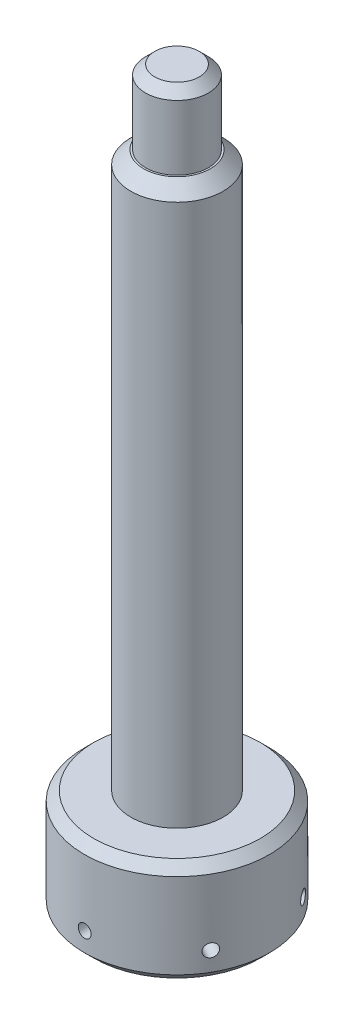
SolidWorks part; units mm, degrees
material "Plain Carbon Steel"
ref_plane "Front Plane" through (0, 0, 0) normal (0, 0, 1) x (1, 0, 0)
ref_plane "Top Plane" through (0, 0, 0) normal (0, 1, 0) x (1, 0, 0)
ref_plane "Right Plane" through (0, 0, 0) normal (1, 0, 0) x (0, 0, -1)
other "Configuration Table"
sketch "Sketch1" plane through (0, 0, 0) normal (0, 1, 0) x (1, 0, 0)
  circle A0 centre (0, 0) radius 6.35
  dimension "D1" = 12.7
extrude "Extrude1" add sketch "Sketch1" along normal blind 4.572
sketch "Sketch4" plane through (0, 0, 0) normal (0, -1, 0) x (1, 0, 0)
  circle A1 centre (0, 0) radius 6.35
  circle A2 centre (0, 0) radius 6.35
  dimension "D1" = 0
extrude "Extrude4" add sketch "Sketch4" along normal blind 1.27
sketch "Sketch5" plane through (0, 4.572, 0) normal (0, 1, 0) x (1, 0, 0)
  circle A1 centre (0, 0) radius 6.35
  circle A2 centre (0, 0) radius 6.35
  dimension "D1" = 0
extrude "Extrude5" add sketch "Sketch5" along normal blind 1.27
sketch "Sketch2" plane through (0, 5.842, 0) normal (0, 1, 0) x (1, 0, 0)
  circle A0 centre (0, 0) radius 3.175
  dimension "D1" = 6.35
extrude "Extrude2" add sketch "Sketch2" along normal blind 38.1
sketch "Sketch3" plane through (0, 43.942, 0) normal (0, 1, 0) x (1, 0, 0)
  circle A0 centre (0, 0) radius 2.159
  dimension "D1" = 4.318
extrude "Extrude3" add sketch "Sketch3" along normal blind 5.08
chamfer "Chamfer1" distance 0.635 angle 45 2 edges at (0, -1.27, -6.35) (0, 5.842, 6.35)
chamfer "Chamfer2" distance 0.889 angle 45 1 edges at (0, 43.942, 3.175)
chamfer "Chamfer3" distance 0.635 angle 45 1 edges at (0, 49.022, 2.159)
ref_point "Point1"
sketch "Sketch6" plane through (0, 0, 0) normal (0, 0, 1) x (1, 0, 0)
  line L0 (0, -0.635) -> (-0.635, -1.27)
  line L1 (-6.35, -0.635) -> (6.35, -0.635) construction
  line L2 (-5.715, -1.27) -> (5.715, -1.27) construction
  line L3 (0, -0.635) -> (0.635, -1.27)
  line L4 (-0.635, -1.27) -> (0.635, -1.27)
extrude "Extrude7" cut sketch "Sketch6" against normal through all and the other way through all
sketch "Sketch7" plane through (0, 0, 0) normal (0, 0, 1) x (1, 0, 0)
  circle A0 centre (0, 0.6799) radius 0.4445
  dimension "D1" = 0.889
extrude "Extrude8" cut sketch "Sketch7" against normal through all and the other way through all
pattern_circular "CirPattern1" count 3 every 120 about axis through (0, 43.942, 0) along (0, -1, 0) of "Extrude8"
